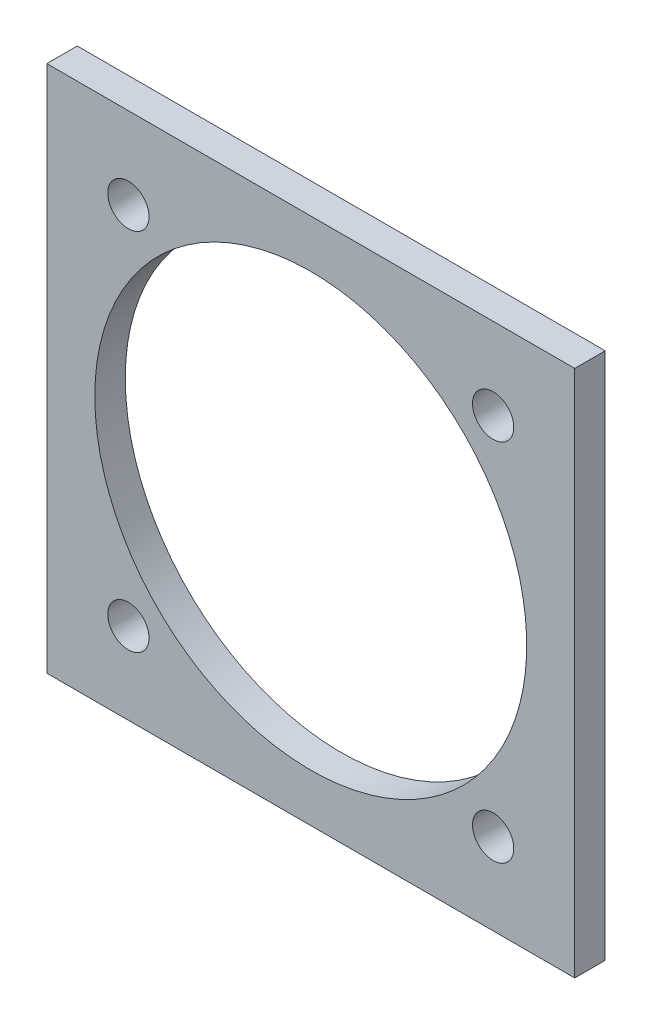
SolidWorks part; units mm, degrees
material "Silicon Rubber"
ref_plane "Front (X-Y)" through (0, 0, 0) normal (0, 0, 1) x (1, 0, 0)
ref_plane "Top (X-Z)" through (0, 0, 0) normal (0, 1, 0) x (1, 0, 0)
ref_plane "Right (Y-Z)" through (0, 0, 0) normal (1, 0, 0) x (0, 0, -1)
ref_axis "X-Axis" through (-27.5, 0, 0) along (1, 0, 0)
ref_axis "Y-Axis" through (0, 27.5, 0) along (0, -1, 0)
ref_axis "Z-Axis" through (0, 0, -0.1588) along (0, 0, 1)
sketch "Sketch1" plane through (0, 0, 0) normal (0, 0, 1) x (1, 0, 0)
  line L0 (0, 27.5) -> (0, 0) construction
  line L1 (27.5, -27.5) -> (-27.5, -27.5)
  line L2 (27.5, -27.5) -> (27.5, 27.5)
  line L3 (27.5, 27.5) -> (-27.5, 27.5)
  line L4 (-27.5, -27.5) -> (-27.5, 27.5)
  line L5 (27.5, -27.5) -> (-27.5, 27.5) construction
  line L6 (27.5, 27.5) -> (-27.5, -27.5) construction
  line L7 (0, 0) -> (27.5, 0) construction
  line L8 (19, 19) -> (-19, 19) construction
  line L9 (-19, 19) -> (-19, -19) construction
  circle A0 centre (0, 0) radius 22.5
  circle A1 centre (19, 19) radius 2.15
  circle A2 centre (19, -19) radius 2.15
  circle A3 centre (-19, -19) radius 2.15
  circle A4 centre (-19, 19) radius 2.15
  point P0 (0, 0)
  dimension "D1" = 38
  dimension "D2" = 4.3
  dimension "D3" = 45
  dimension "D4" = 55
extrude "Boss-Extrude1" add sketch "Sketch1" along normal blind 3.175
